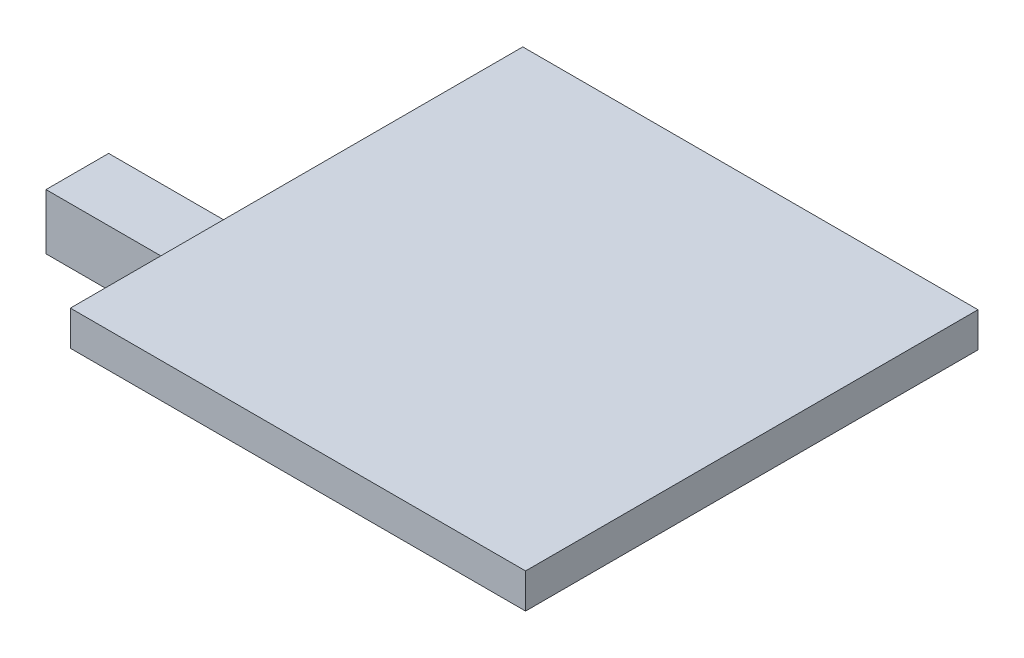
SolidWorks part; units mm, degrees
ref_plane "Front Plane" through (0, 0, 0) normal (0, 0, 1) x (1, 0, 0)
ref_plane "Top Plane" through (0, 0, 0) normal (0, 1, 0) x (1, 0, 0)
ref_plane "Right Plane" through (0, 0, 0) normal (1, 0, 0) x (0, 0, -1)
sketch "Sketch1" plane through (0, 0, 0) normal (0, 0, 1) x (1, 0, 0)
  line L0 (-65.5935, -8.0113) -> (-65.5935, -18.0113)
  line L1 (-65.5935, -18.0113) -> (65.2065, -18.0113)
  line L2 (65.2065, -18.0113) -> (65.2065, -8.0113)
  line L3 (65.2065, -8.0113) -> (-65.5935, -8.0113)
  dimension "D1" = 130.8
  dimension "D2" = 10
extrude "Boss-Extrude1" add sketch "Sketch1" along normal blind 130
sketch "Sketch3" plane through (0, -18.0113, 0) normal (0, -1, 0) x (1, 0, 0)
  line L0 (-65.5935, 85) -> (-37.6211, 85) construction
  line L1 (-65.5935, 130) -> (-65.5935, 0) construction
  line L2 (-65.5935, 76) -> (-55.5935, 76)
  line L3 (-55.5935, 76) -> (-55.5935, 94)
  line L4 (-55.5935, 94) -> (-65.5935, 94)
  line L5 (-65.5935, 94) -> (-65.5935, 76)
  line L6 (-65.5935, 65) -> (-69.4095, 65) construction
  point P4 (-65.5935, 65)
  dimension "D1" = 20
  dimension "D2" = 9
  dimension "D3" = 9
  dimension "D4" = 10
extrude "Boss-Extrude2" add sketch "Sketch3" along normal blind 16
sketch "Sketch4" plane through (-65.5935, 0, 0) normal (-1, 0, 0) x (0, 0, 1)
  line L0 (76, -18.0113) -> (94, -18.0113)
  line L1 (94, -18.0113) -> (94, -34.0113)
  line L2 (94, -34.0113) -> (76, -34.0113)
  line L3 (76, -34.0113) -> (76, -18.0113)
extrude "Boss-Extrude3" add sketch "Sketch4" along normal blind 43
sketch "Sketch5" plane through (0, 0, 94) normal (0, 0, 1) x (1, 0, 0)
  line L5 (-65.5935, -18.0113) -> (-57.5935, -18.0113)
  line L6 (-65.5935, -18.0113) -> (65.2065, -18.0113) construction
  line L7 (-57.5935, -18.0113) -> (-57.5935, -34.0113)
  line L8 (-55.5935, -34.0113) -> (-108.5935, -34.0113) construction
  line L9 (-57.5935, -34.0113) -> (-65.5935, -34.0113)
  line L10 (-65.5935, -34.0113) -> (-65.5935, -18.0113)
  dimension "D1" = 8
extrude "Boss-Extrude4" add sketch "Sketch5" along normal blind 10
sketch "Sketch6" plane through (0, 0, 76) normal (0, 0, -1) x (-1, 0, 0)
  line L0 (65.5935, -18.0113) -> (57.5935, -18.0113)
  line L1 (65.5935, -18.0113) -> (-65.2065, -18.0113) construction
  line L2 (57.5935, -18.0113) -> (57.5935, -34.0113)
  line L3 (108.5935, -34.0113) -> (55.5935, -34.0113) construction
  line L4 (57.5935, -34.0113) -> (65.5935, -34.0113)
  line L5 (65.5935, -34.0113) -> (65.5935, -18.0113)
  dimension "D1" = 8
extrude "Boss-Extrude5" add sketch "Sketch6" along normal blind 10
sketch "Sketch7" plane through (0, 0, 76) normal (0, 0, -1) x (-1, 0, 0)
  line L0 (57.5935, -18.0113) -> (55.5935, -18.0113)
  line L1 (55.5935, -18.0113) -> (55.5935, -34.0113)
  line L2 (55.5935, -34.0113) -> (57.5935, -34.0113)
  line L3 (57.5935, -34.0113) -> (57.5935, -18.0113)
extrude "Cut-Extrude1" cut sketch "Sketch7" against normal blind 20
